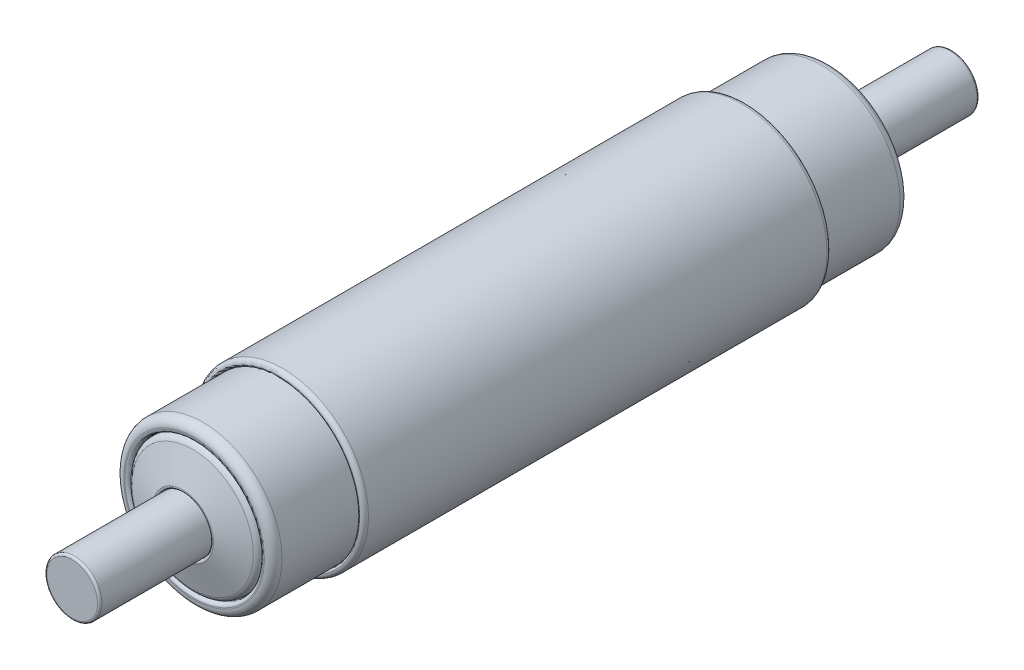
SolidWorks part; units mm, degrees
ref_plane "Front Plane" through (0, 0, 0) normal (0, 0, 1) x (1, 0, 0)
ref_plane "Top Plane" through (0, 0, 0) normal (0, 1, 0) x (1, 0, 0)
ref_plane "Right Plane" through (0, 0, 0) normal (1, 0, 0) x (0, 0, -1)
sketch "Sketch1" plane through (0, 0, 0) normal (1, 0, 0) x (0, 0, -1)
  line L0 (-38.1, 9.144) -> (38.1, 9.144) construction
  line L1 (-50.8, 3.175) -> (50.8, 3.175)
  line L2 (-50.8, 3.175) -> (-50.8, -3.175)
  line L3 (-50.8, -3.175) -> (50.8, -3.175)
  line L4 (50.8, 3.175) -> (50.8, -3.175)
  line L5 (0, -3.175) -> (0, 3.175) construction
  line L6 (-50.8, 0) -> (50.8, 0) construction
  line L7 (-38.1, -9.906) -> (38.1, -9.906)
  line L8 (-38.1, -9.906) -> (-38.1, 9.906)
  line L9 (-38.1, 9.906) -> (38.1, 9.906)
  line L10 (38.1, -9.906) -> (38.1, 9.906)
  line L11 (0, 9.906) -> (0, -9.906) construction
  line L12 (-38.1, 0) -> (38.1, 0) construction
  line L13 (26.9875, -9.906) -> (-26.9875, -9.906)
  line L14 (26.9875, -9.906) -> (26.9875, 9.906)
  line L15 (26.9875, 9.906) -> (-26.9875, 9.906)
  line L16 (-26.9875, -9.906) -> (-26.9875, 9.906)
  line L17 (0, 9.906) -> (0, -9.906) construction
  line L18 (26.9875, 0) -> (-26.9875, 0) construction
  line L19 (26.9875, 8.382) -> (-26.9875, 8.382) construction
  line L20 (-26.9875, 8.382) -> (-38.1, 8.382) construction
  line L21 (26.9875, 8.382) -> (38.1, 8.382) construction
  point P0 (0, 0)
  point P1 (0, 0)
  point P6 (0, 0)
  point P13 (0, 0)
  point P20 (-38.1, -3.175)
  point P21 (38.1, -3.175)
  point P26 (-11.176, 0)
  point P27 (11.176, 0)
  point P28 (0, 8.382)
  point P29 (-38.1, 8.382)
  point P35 (-26.9875, 9.906)
  dimension "Axle Diameter" = 6.35
  dimension "Overall Width" = 101.6
  dimension "Roller Width" = 53.975
  dimension "For Between Frame Width" = 76.2
  dimension "Roller Diameter" = 19.812
  dimension "D1" = 39.624
  dimension "D2" = 39.624
  dimension "Roller Thickness" = 1.524
  dimension "D3" = 0.762
sketch "Sketch2" plane through (0, 0, 0) normal (0, 0, 1) x (1, 0, 0)
  circle A0 centre (0, 0) radius 9.906
  circle A1 centre (0, 0) radius 3.175
  point P6 (-9.906, 0)
  point P7 (9.906, 0)
sketch "Sketch3" plane through (0, 0, 0) normal (1, 0, 0) x (0, 0, -1)
  line L0 (-26.9875, 9.144) -> (26.9875, 9.144)
  line L1 (-50.8, 3.175) -> (50.8, 3.175)
  line L2 (-50.8, 3.175) -> (-50.8, 0)
  line L3 (-50.8, 0) -> (50.8, 0)
  line L4 (50.8, 3.175) -> (50.8, 0)
  line L5 (-26.9875, 9.906) -> (26.9875, 9.906)
  line L6 (-26.9875, 9.906) -> (-26.9875, 9.144)
  line L7 (-26.9875, 3.2004) -> (26.9875, 3.2004) construction
  line L8 (26.9875, 9.906) -> (26.9875, 9.144)
  line L10 (-38.1, 9.144) -> (38.1, 9.144) construction
  line L11 (-26.9875, -9.906) -> (-26.9875, 9.906) construction
  dimension "D1" = 0.0254
revolve "Revolve1" add sketch "Sketch3" angle 360 about L3
fillet "Fillet1" radius 0.508 2 edges at (9.906, 0, -26.9875) (9.906, 0, 26.9875)
sketch "Sketch4" plane through (0, 0, 0) normal (1, 0, 0) x (0, 0, -1)
  line L0 (36.7225, 9.144) -> (-36.7225, 9.144)
  line L1 (-38.1, 9.144) -> (38.1, 9.144) construction
  line L3 (-50.8, 3.175) -> (50.8, 3.175) construction
  line L4 (-38.1, -9.906) -> (-38.1, 9.906) construction
  line L5 (-38.1, 3.175) -> (38.1, 3.175)
  line L8 (-38.1, 3.175) -> (-36.7225, 7.5438)
  line L9 (-36.7225, 7.5438) -> (36.7225, 7.5438)
  line L10 (36.7225, 7.5438) -> (38.1, 3.175)
  line L11 (0, 7.5438) -> (0, 0) construction
  line L12 (-36.7225, 9.144) -> (-36.7225, 7.62)
  line L13 (-36.7225, 7.62) -> (36.7225, 7.62)
  line L14 (36.7225, 7.62) -> (36.7225, 9.144)
  dimension "D1" = 17.5
  dimension "D2" = 1.6002
  dimension "D3" = 0.0762
revolve "Revolve2" add sketch "Sketch4" angle 360 about L6
fillet "Fillet2" radius 0.762 2 edges at (0, -7.5438, -36.7225) (0, -7.5438, 36.7225)
fillet "Fillet3" radius 1.016 2 edges at (0, -9.144, 36.7225) (0, -9.144, -36.7225)
fillet "Fillet4" radius 0.254 2 edges at (0, -3.175, -38.1) (0, -3.175, 38.1)
fillet "Fillet5" radius 0.381 2 edges at (0, -7.62, 36.7225) (0, -7.62, -36.7225)
fillet "Fillet6" radius 0.254 2 edges at (3.175, 0, -50.8) (3.175, 0, 50.8)
fillet "Fillet7" radius 0.254 2 edges at (9.144, 0, 26.9875) (9.144, 0, -26.9875)
equation "\"D1@Sketch1\"=\"Roller Diameter@Sketch1\"*2"
equation "\"D2@Sketch1\"=\"D1@Sketch1\""
equation "\"D1@Fillet1\"=\"Roller Thickness@Sketch1\"/3"
equation "\"D3@Sketch1\"=\"Roller Thickness@Sketch1\"*.5"
